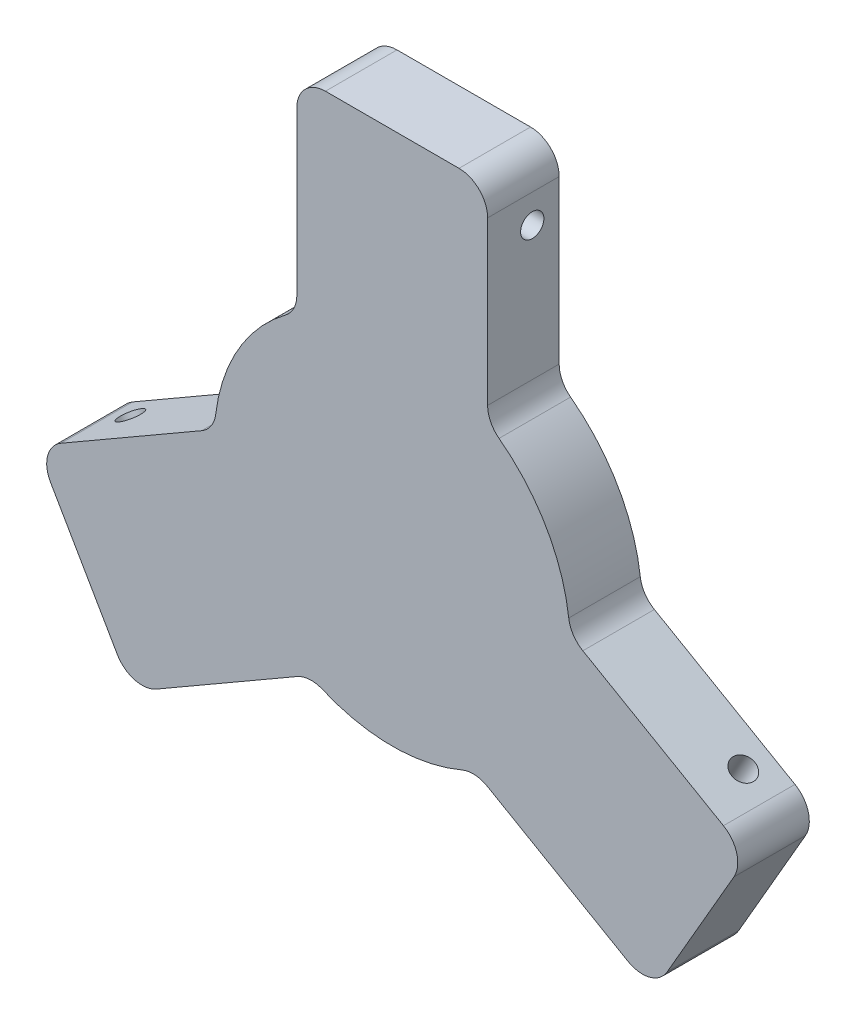
SolidWorks part; units mm, degrees
ref_plane "Front Plane" through (0, 0, 0) normal (0, 0, 1) x (1, 0, 0)
ref_plane "Top Plane" through (0, 0, 0) normal (0, 1, 0) x (1, 0, 0)
ref_plane "Right Plane" through (0, 0, 0) normal (1, 0, 0) x (0, 0, -1)
sketch "Sketch1" plane through (0, 0, 0) normal (0, 0, 1) x (1, 0, 0)
  line L0 (12.7, 21.9691) -> (12.7, 43.5864)
  line L1 (12.6758, -21.9831) -> (31.3969, -32.7917)
  line L2 (8.89, 47.3964) -> (-8.89, 47.3964)
  line L3 (-12.7, 21.9691) -> (-12.7, 43.5864)
  line L4 (25.3758, 0.014) -> (44.0969, -10.7947)
  line L5 (36.6015, -31.3972) -> (45.4915, -15.9992)
  line L6 (-25.3758, 0.014) -> (-44.0969, -10.7947)
  line L7 (-12.6758, -21.9831) -> (-31.3969, -32.7917)
  line L8 (-45.4915, -15.9992) -> (-36.6015, -31.3972)
  arc A0 (-14.2211, 18.9233) -> (-23.4986, 2.8542) centre (0, 0) ccw
  arc A1 (-9.2775, -21.7774) -> (9.2775, -21.7774) centre (0, 0) ccw
  arc A2 (23.4986, 2.8542) -> (14.2211, 18.9233) centre (0, 0) ccw
  arc A3 (-12.7, 21.9691) -> (-14.2211, 18.9233) centre (-16.51, 21.9691) cw
  arc A4 (-25.3758, 0.014) -> (-23.4986, 2.8542) centre (-27.2808, 3.3135) ccw
  arc A5 (-44.0969, -10.7947) -> (-45.4915, -15.9992) centre (-42.1919, -14.0942) ccw
  arc A6 (-31.3969, -32.7917) -> (-36.6015, -31.3972) centre (-33.3019, -29.4922) cw
  arc A7 (-12.6758, -21.9831) -> (-9.2775, -21.7774) centre (-10.7708, -25.2826) cw
  arc A8 (12.6758, -21.9831) -> (9.2775, -21.7774) centre (10.7708, -25.2826) ccw
  arc A9 (31.3969, -32.7917) -> (36.6015, -31.3972) centre (33.3019, -29.4922) ccw
  arc A10 (44.0969, -10.7947) -> (45.4915, -15.9992) centre (42.1919, -14.0942) cw
  arc A11 (25.3758, 0.014) -> (23.4986, 2.8542) centre (27.2808, 3.3135) cw
  arc A12 (12.7, 21.9691) -> (14.2211, 18.9233) centre (16.51, 21.9691) ccw
  arc A13 (12.7, 43.5864) -> (8.89, 47.3964) centre (8.89, 43.5864) ccw
  arc A14 (-8.89, 47.3964) -> (-12.7, 43.5864) centre (-8.89, 43.5864) ccw
  point P17 (0, 0)
  point P37 (12.7, 47.3964)
  point P40 (-12.7, 47.3964)
  dimension "D1" = 47.3964
  dimension "D5" = 3.81
  dimension "D2" = 25.4
  dimension "D3" = 12.7
  dimension "D4" = 3
extrude "Boss-Extrude1" add sketch "Sketch1" along normal blind 9.525
sketch "Sketch3" plane through (-6.35, -10.9985, 0) normal (-0.5, -0.866, 0) x (0.866, -0.5, 0)
  circle A0 centre (39.7764, 3.582) radius 1.55 construction
  circle A1 centre (39.7764, 3.582) radius 1.55
extrude "Cut-Extrude2" cut sketch "Sketch3" against normal blind 5.08 contours A1
sketch "Sketch4" plane through (6.35, 10.9985, 0) normal (0.5, 0.866, 0) x (0.866, -0.5, 0)
  circle A0 centre (39.7764, -3.582) radius 1.55 construction
  circle A1 centre (39.7764, -3.582) radius 1.55
extrude "Cut-Extrude3" cut sketch "Sketch4" against normal blind 5.08
ref_axis "Axis3" through (0, 0, 0) along (0, 0, -1)
pattern_circular "CirPattern2" count 3 over 360 about axis through (0, 0, 0) along (0, 0, -1) of "Cut-Extrude2", "Cut-Extrude3"
